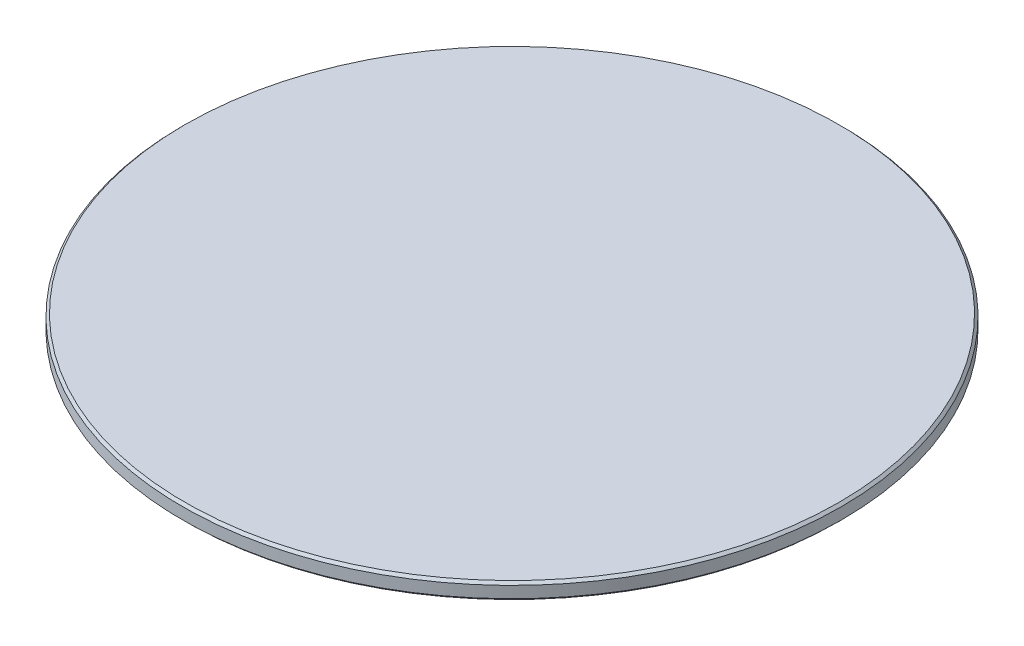
SolidWorks part; units mm, degrees
material "Verre"
ref_plane "Plan de face" through (0, 0, 0) normal (0, 0, 1) x (1, 0, 0)
ref_plane "Plan de dessus" through (0, 0, 0) normal (0, 1, 0) x (1, 0, 0)
ref_plane "Plan de droite" through (0, 0, 0) normal (1, 0, 0) x (0, 0, -1)
sketch "Esquisse1" plane through (0, 0, 0) normal (0, 0, 1) x (1, 0, 0)
  line L0 (0, 0) -> (19.85, 0)
  line L1 (20, 0.15) -> (20, 0.85)
  line L2 (0, 1) -> (0, 0) construction
  line L3 (0, 0) -> (0, 1)
  line L4 (19.85, 1) -> (0, 1)
  line L5 (20, 0.85) -> (19.85, 1)
  line L6 (19.85, 0) -> (20, 0.15)
  point P1 (20, 0)
  point P4 (20, 1)
  dimension "D1" = 20
  dimension "D3" = 1
revolve "Révolution1" add sketch "Esquisse1" angle 360 about L2
